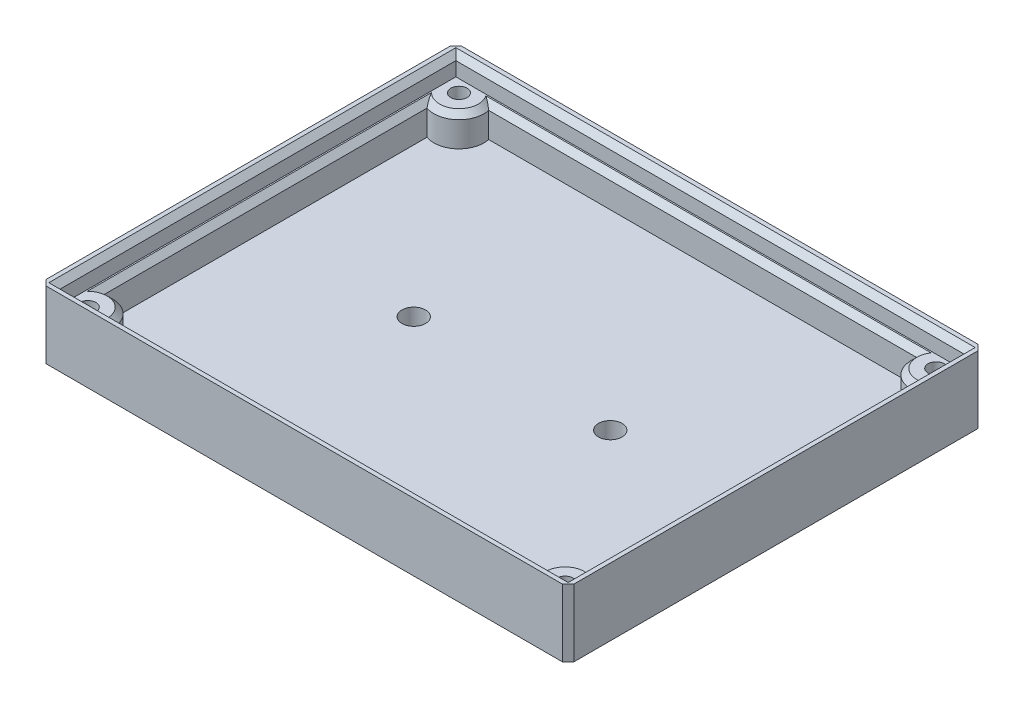
SolidWorks part; units mm, degrees
ref_plane "Front Plane" through (0, 0, 0) normal (0, 0, 1) x (1, 0, 0)
ref_plane "Top Plane" through (0, 0, 0) normal (0, 1, 0) x (1, 0, 0)
ref_plane "Right Plane" through (0, 0, 0) normal (1, 0, 0) x (0, 0, -1)
sketch "Sketch1" plane through (0, 0, 0) normal (0, 1, 0) x (1, 0, 0)
  line L0 (-47, -37) -> (-47, 37)
  line L1 (-45, -35) -> (45, -35) construction
  line L2 (-45, -35) -> (-45, 35) construction
  line L3 (-45, 35) -> (45, 35) construction
  line L4 (45, -35) -> (45, 35) construction
  line L5 (-45, -35) -> (45, 35) construction
  line L6 (-45, 35) -> (45, -35) construction
  line L7 (-47, 37) -> (47, 37)
  line L8 (47, -37) -> (47, 37)
  line L9 (-47, -37) -> (47, -37)
  point P0 (0, 0)
  dimension "D1" = 90
  dimension "D2" = 70
  dimension "D3" = 2
extrude "Boss-Extrude1" add sketch "Sketch1" along normal blind 12
sketch "Sketch2" plane through (0, 12, 0) normal (0, 1, 0) x (1, 0, 0)
  line L1 (-45.25, -35.25) -> (45.25, -35.25)
  line L2 (-45.25, -35.25) -> (-45.25, 35.25)
  line L3 (-45.25, 35.25) -> (45.25, 35.25)
  line L4 (45.25, -35.25) -> (45.25, 35.25)
  line L5 (-45.25, -35.25) -> (45.25, 35.25) construction
  line L6 (-45.25, 35.25) -> (45.25, -35.25) construction
  point P0 (0, 0)
  dimension "D1" = 90.5
  dimension "D2" = 70.5
extrude "Cut-Extrude1" cut sketch "Sketch2" against normal blind 3.5
sketch "Sketch3" plane through (0, 8.5, 0) normal (0, 1, 0) x (1, 0, 0)
  line L1 (45, -35) -> (-45, -35) construction
  line L2 (45, -35) -> (45, 35) construction
  line L3 (45, 35) -> (-45, 35) construction
  line L4 (-45, -35) -> (-45, 35) construction
  line L5 (45, -35) -> (-45, 35) construction
  line L6 (45, 35) -> (-45, -35) construction
  circle A0 centre (-42.5, 33.0556) radius 1.45
  circle A1 centre (42.5, 33.0556) radius 1.45
  circle A2 centre (42.5, -33.0556) radius 1.45
  circle A3 centre (-42.5, -33.0556) radius 1.45
  point P0 (0, 0)
  dimension "D4" = 2.9
  dimension "D1" = 90
  dimension "D2" = 70
  dimension "D3" = 2.5
extrude "Cut-Extrude2" cut sketch "Sketch3" against normal blind 6
shell "Shell1" thickness 3 removed face at (-42.5, 8.5, 34.5056)
chamfer "Chamfer1" distance 1 angle 45 4 edges at (45.25, 12, 0) (0, 12, 35.25) (-45.25, 12, 0) (0, 12, -35.25) tangent propagation no
chamfer "Chamfer2" distance 1 angle 45 8 edges at (0, 8.5, 34) (-39.5643, 8.5, 29.7113) (-44, 8.5, 0) (39.5643, 8.5, 29.7113) (44, 8.5, 0) (39.5643, 8.5, -29.7113) (0, 8.5, -34) (-39.5643, 8.5, -29.7113)
chamfer "Chamfer3" distance 1 angle 45 4 edges at (-47, 6, -37) (47, 6, -37) (47, 6, 37) (-47, 6, 37)
sketch "Sketch4" plane through (0, 3, 0) normal (0, 1, 0) x (1, 0, 0)
  circle A0 centre (-17.5, 0) radius 2.1
  circle A1 centre (17.5, 0) radius 2.1
  dimension "D3" = 4.2
  dimension "D1" = 17.5
  dimension "D2" = 35
extrude "Cut-Extrude3" cut sketch "Sketch4" against normal through all
